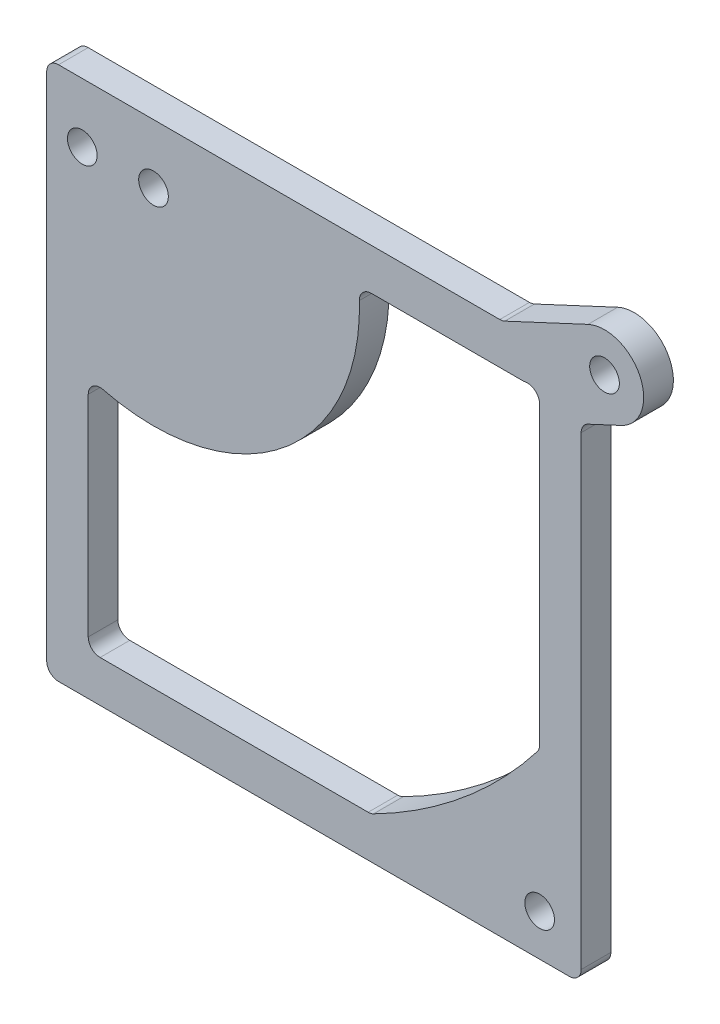
SolidWorks part; units mm, degrees
ref_plane "Front Plane" through (0, 0, 0) normal (0, 0, 1) x (1, 0, 0)
ref_plane "Top Plane" through (0, 0, 0) normal (0, 1, 0) x (1, 0, 0)
ref_plane "Right Plane" through (0, 0, 0) normal (1, 0, 0) x (0, 0, -1)
sketch "Sketch1" plane through (0, 0, 0) normal (0, 0, 1) x (1, 0, 0)
  line L1 (-54.61, -57.1594) -> (54.7003, -57.1594)
  line L2 (-57.15, -54.6194) -> (-57.15, 54.6194)
  line L3 (-54.6194, 57.15) -> (39.8219, 57.15)
  line L4 (57.2403, -54.6194) -> (57.2403, 44.8946)
  line L5 (-57.15, -57.1594) -> (-56.4061, -56.4154) construction
  line L17 (40.8953, 57.388) -> (58.694, 65.6877)
  line L19 (52.6597, -56.132) -> (57.2403, -57.1594) construction
  line L24 (-45.72, -48.26) -> (11.6497, -48.26)
  line L25 (-48.26, -45.72) -> (-48.26, -0.7521)
  line L27 (48.3503, -17.3969) -> (48.3503, 45.8059)
  line L29 (-48.26, 48.26) -> (33.8079, -33.8079) construction
  line L30 (12.3175, 48.26) -> (45.0315, 48.26)
  line L31 (48.3503, -17.3969) -> (48.3503, -48.26) construction
  line L32 (11.6497, -48.26) -> (48.3503, -48.26) construction
  line L33 (58.7068, 47.1966) -> (65.7788, 50.4943)
  arc A13 (-54.61, -57.1594) -> (-57.15, -54.6194) centre (-54.61, -54.6194) cw
  arc A14 (54.7003, -57.1594) -> (57.2403, -54.6194) centre (54.7003, -54.6194) ccw
  arc A16 (-57.15, 54.6194) -> (-54.6194, 57.15) centre (-54.6194, 54.6194) cw
  circle A17 centre (-49.53, 44.45) radius 3.175
  circle A18 centre (-34.29, 44.45) radius 3.175
  arc A34 (-45.0973, 1.7104) -> (9.7785, 45.6508) centre (-34.29, 44.45) ccw
  arc A36 (12.8028, -47.9832) -> (47.8207, -18.9492) centre (-34.29, 44.45) ccw
  arc A37 (-45.0973, 1.7104) -> (-48.26, -0.7521) centre (-45.72, -0.7521) ccw
  arc A38 (-45.72, -48.26) -> (-48.26, -45.72) centre (-45.72, -45.72) cw
  arc A39 (12.8028, -47.9832) -> (11.6497, -48.26) centre (11.6497, -45.72) cw
  arc A40 (48.3503, -17.3969) -> (47.8207, -18.9492) centre (45.8103, -17.3969) cw
  arc A41 (45.0315, 48.26) -> (48.3503, 45.8059) centre (45.72, 45.72) cw
  arc A42 (9.7785, 45.6508) -> (12.3175, 48.26) centre (12.3175, 45.72) cw
  circle A44 centre (48.3503, -48.26) radius 3.175
  circle A45 centre (62.2364, 58.091) radius 3.175
  arc A47 (65.7788, 50.4943) -> (58.694, 65.6877) centre (62.2364, 58.091) ccw
  arc A48 (58.7068, 47.1966) -> (57.2403, 44.8946) centre (59.7803, 44.8946) ccw
  arc A49 (40.8953, 57.388) -> (39.8219, 57.15) centre (39.8219, 59.69) cw
  point P0 (0, 0)
  point P9 (0, 0)
  point P10 (0, 0)
  point P12 (62.2364, 58.091)
  point P16 (0, 0)
  dimension "D4" = 6.35
  dimension "D5" = 16.764
  dimension "D6" = 2.54
  dimension "D9" = 6.35
  dimension "D11" = 2.54
  dimension "D12" = 6.35
  dimension "D10" = 2.54
  dimension "D1" = 7.62
  dimension "D2" = 8.89
  dimension "D3" = 12.7
  dimension "D7" = 22.86
  dimension "D8" = 12.7
  dimension "D13" = 65
extrude "Boss-Extrude1" add sketch "Sketch1" along normal mid plane 6.35
